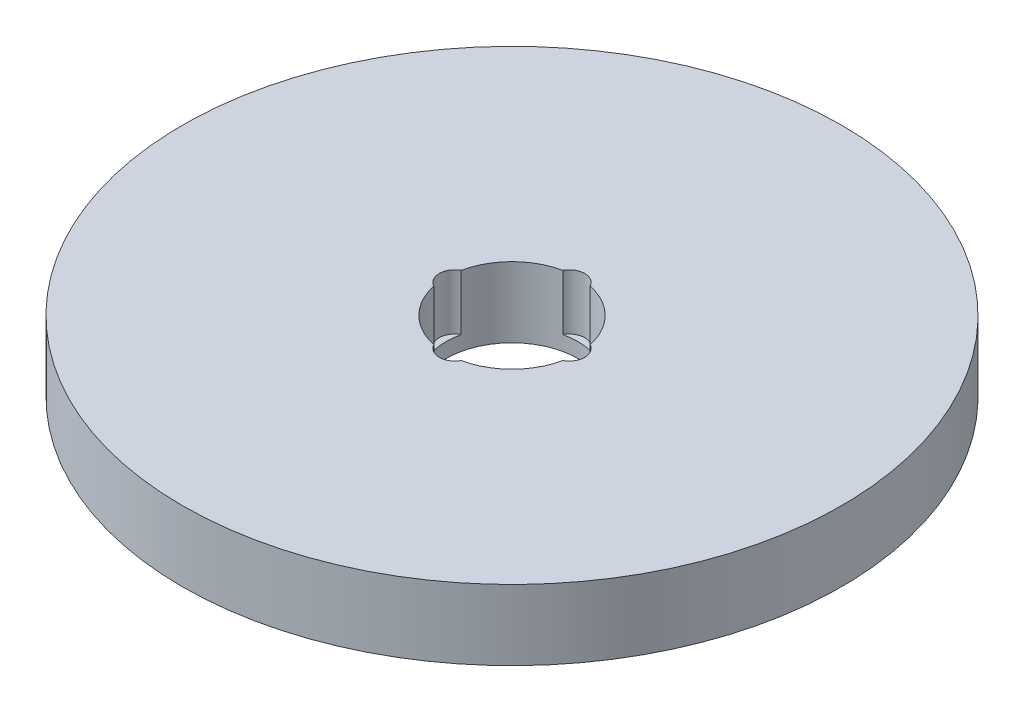
SolidWorks part; units mm, degrees
ref_plane "Front Plane" through (0, 0, 0) normal (0, 0, 1) x (1, 0, 0)
ref_plane "Top Plane" through (0, 0, 0) normal (0, 1, 0) x (1, 0, 0)
ref_plane "Right Plane" through (0, 0, 0) normal (1, 0, 0) x (0, 0, -1)
sketch "Sketch1" plane through (0, 0, 0) normal (0, 1, 0) x (1, 0, 0)
  circle A0 centre (0, 0) radius 37.5
  dimension "FLANGE_OD" = 75
extrude "Boss-Extrude1" add sketch "Sketch1" along normal blind 8
sketch "Sketch2" plane through (0, 0, 0) normal (0, 1, 0) x (1, 0, 0)
  circle A0 centre (0, 0) radius 7.5
  dimension "BORE_D" = 15
extrude "Cut-Extrude1" cut sketch "Sketch2" along normal through all
sketch "Sketch3" plane through (0, 8, 0) normal (0, 1, 0) x (1, 0, 0)
  circle A0 centre (0, 0) radius 6.4993 construction
  circle A1 centre (-6.4993, 0) radius 1.7701
  dimension "BOLT_D" = 3.5401
  dimension "BOLT_PCD" = 12.9985
extrude "Cut-Extrude2" cut sketch "Sketch3" against normal blind 6.3311
pattern_circular "CirPattern1" count 4 over 360 about axis through (0, 0, 0) along (0, 1, 0) of "Cut-Extrude2"
